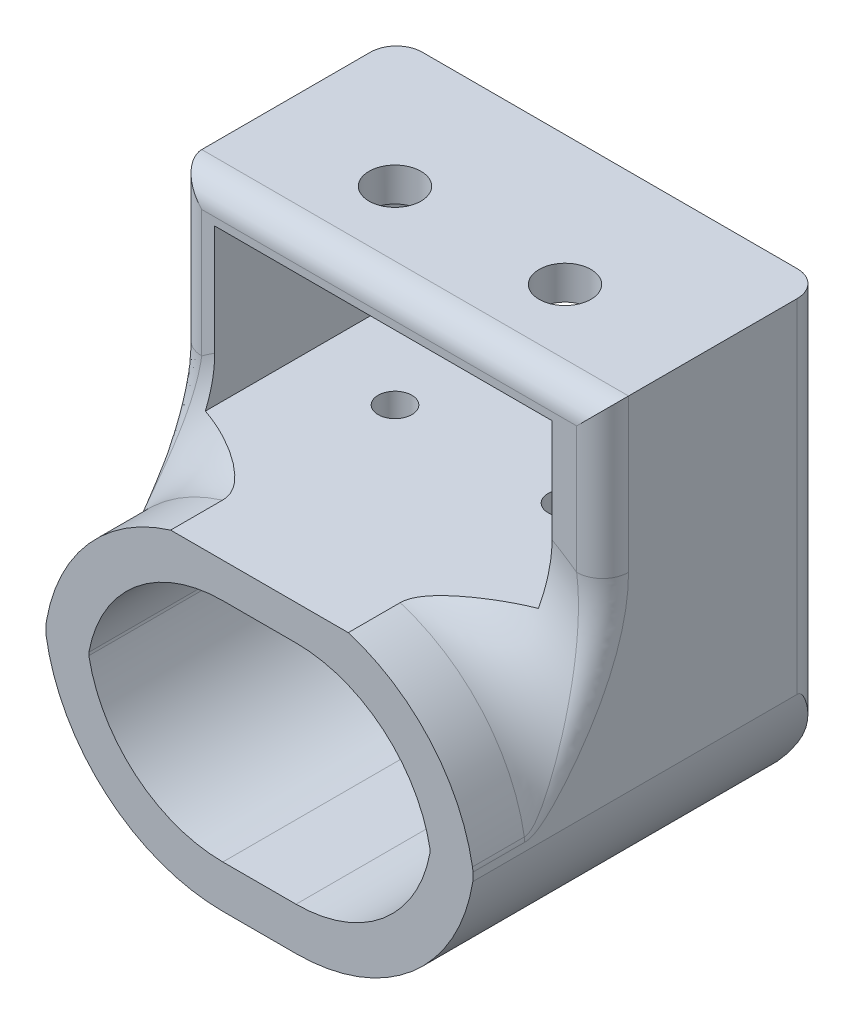
SolidWorks part; units mm, degrees
ref_plane "Front Plane" through (0, 0, 0) normal (0, 0, 1) x (1, 0, 0)
ref_plane "Top Plane" through (0, 0, 0) normal (0, 1, 0) x (1, 0, 0)
ref_plane "Right Plane" through (0, 0, 0) normal (1, 0, 0) x (0, 0, -1)
sketch "Sketch1" plane through (0, 0, 0) normal (0, 0, 1) x (1, 0, 0)
  line L2 (2.7649, 6.6874) -> (-0.0551, 6.6874)
  line L3 (-6.8689, 0.8749) -> (-6.8689, 0.48)
  line L4 (2.7649, 5.1874) -> (-0.0551, 5.1874)
  line L5 (-0.0551, -3.8326) -> (2.7649, -3.8326)
  line L6 (-0.0551, -5.3326) -> (2.7649, -5.3326)
  line L7 (-5.3689, 0.7486) -> (-5.3689, 0.6062)
  line L8 (8.0787, 0.7486) -> (8.0787, 0.6062)
  line L9 (9.5787, 0.8749) -> (9.5787, 0.48)
  arc A4 (8.0787, 0.7486) -> (2.7649, 5.1874) centre (2.7649, -0.2126) ccw
  arc A5 (-0.0551, 5.1874) -> (-5.3689, 0.7486) centre (-0.0551, -0.2126) ccw
  arc A6 (-5.3689, 0.6062) -> (-0.0551, -3.8326) centre (-0.0551, 1.5674) ccw
  arc A7 (2.7649, -3.8326) -> (8.0787, 0.6062) centre (2.7649, 1.5674) ccw
  arc A8 (-0.0551, 6.6874) -> (-6.8689, 0.8749) centre (-0.0551, -0.2126) ccw
  arc A9 (-6.8689, 0.48) -> (-0.0551, -5.3326) centre (-0.0551, 1.5674) ccw
  arc A10 (2.7649, -5.3326) -> (9.5787, 0.48) centre (2.7649, 1.5674) ccw
  arc A11 (9.5787, 0.8749) -> (2.7649, 6.6874) centre (2.7649, -0.2126) ccw
  dimension "D1" = 1.5
extrude "Boss-Extrude1" add sketch "Sketch1" along normal blind 12
sketch "Sketch2" plane through (0, 0, 0) normal (0, 0, -1) x (-1, 0, 0)
  line L4 (-9.5787, 0.8749) -> (-9.5787, 0.48)
  line L5 (-2.7649, -5.3326) -> (0.0551, -5.3326)
  line L6 (6.8689, 0.48) -> (6.8689, 0.8749)
  line L7 (0.0551, 6.6874) -> (-2.7649, 6.6874)
  line L8 (-9.5787, 0.8749) -> (-9.5787, 0.48)
  line L9 (-2.7649, -5.3326) -> (0.0551, -5.3326)
  line L10 (6.8689, 0.48) -> (6.8689, 0.8749)
  line L11 (0.0551, 6.6874) -> (-2.7649, 6.6874)
  arc A4 (-2.7649, 6.6874) -> (-9.5787, 0.8749) centre (-2.7649, -0.2126) ccw
  arc A5 (-9.5787, 0.48) -> (-2.7649, -5.3326) centre (-2.7649, 1.5674) ccw
  arc A6 (0.0551, -5.3326) -> (6.8689, 0.48) centre (0.0551, 1.5674) ccw
  arc A7 (6.8689, 0.8749) -> (0.0551, 6.6874) centre (0.0551, -0.2126) ccw
  arc A8 (-2.7649, 6.6874) -> (-9.5787, 0.8749) centre (-2.7649, -0.2126) ccw
  arc A9 (-9.5787, 0.48) -> (-2.7649, -5.3326) centre (-2.7649, 1.5674) ccw
  arc A10 (0.0551, -5.3326) -> (6.8689, 0.48) centre (0.0551, 1.5674) ccw
  arc A11 (6.8689, 0.8749) -> (0.0551, 6.6874) centre (0.0551, -0.2126) ccw
  dimension "D1" = 0
extrude "Boss-Extrude2" add sketch "Sketch2" along normal blind 1.5
sketch "Sketch3" plane through (0, 6.6874, 0) normal (0, 1, 0) x (1, 0, 0)
  line L0 (9.5787, -12) -> (9.5787, 1.5) construction
  line L1 (-6.8689, -12) -> (-6.8689, 1.5) construction
  line L2 (9.5787, -12) -> (9.5787, 1.5)
  line L3 (-6.8689, -12) -> (-6.8689, 1.5)
  line L4 (-6.8689, 1.5) -> (9.5787, 1.5)
  line L5 (-6.8689, -12) -> (9.5787, -12)
extrude "Boss-Extrude3" add sketch "Sketch3" along normal blind 7
sketch "Sketch4" plane through (0, 6.6874, 0) normal (0, -1, 0) x (1, 0, 0)
  line L4 (-0.0551, -1.5) -> (-0.0551, 12)
  line L5 (-0.0551, 12) -> (-6.8689, 12)
  line L6 (-6.8689, 12) -> (-6.8689, -1.5)
  line L7 (-6.8689, -1.5) -> (-0.0551, -1.5)
  line L8 (-0.0551, -1.5) -> (-0.0551, 12)
  line L9 (-0.0551, 12) -> (-6.8689, 12)
  line L10 (-6.8689, 12) -> (-6.8689, -1.5)
  line L11 (-6.8689, -1.5) -> (-0.0551, -1.5)
  dimension "D1" = 0
extrude "Boss-Extrude4" add sketch "Sketch4" along normal up to surface (5.8125 mm away) up to face at (-3.9976, 4.409, 5.25)
sketch "Sketch5" plane through (0, 6.6874, 0) normal (0, -1, 0) x (1, 0, 0)
  line L4 (9.5787, 12) -> (2.7649, 12)
  line L5 (2.7649, 12) -> (2.7649, -1.5)
  line L6 (2.7649, -1.5) -> (9.5787, -1.5)
  line L7 (9.5787, -1.5) -> (9.5787, 12)
  line L8 (9.5787, 12) -> (2.7649, 12)
  line L9 (2.7649, 12) -> (2.7649, -1.5)
  line L10 (2.7649, -1.5) -> (9.5787, -1.5)
  line L11 (9.5787, -1.5) -> (9.5787, 12)
  dimension "D1" = 0
extrude "Boss-Extrude5" add sketch "Sketch5" along normal up to surface up to face at (6.7074, 4.409, 5.25)
sketch "Sketch6" plane through (0, 0, 12) normal (0, 0, 1) x (1, 0, 0)
  line L0 (-5.3689, 12.3874) -> (7.6311, 12.3874)
  line L2 (7.6311, 12.3874) -> (7.6311, 6.3874)
  line L3 (-5.3689, 12.3874) -> (-5.3689, 6.3874)
  line L4 (-5.3689, 6.3874) -> (7.6311, 6.3874)
  dimension "D3" = 6
  dimension "D4" = 13
extrude "Cut-Extrude1" cut sketch "Sketch6" against normal blind 12
sketch "Sketch7" plane through (0, 13.6874, 0) normal (0, 1, 0) x (1, 0, 0)
  circle A0 centre (4.6311, -3.5) radius 1
  circle A1 centre (-1.9213, -3.5) radius 1
  dimension "D3" = 2
extrude "Cut-Extrude2" cut sketch "Sketch7" against normal blind 4
sketch "Sketch8" plane through (0, 6.3874, 0) normal (0, 1, 0) x (1, 0, 0)
  circle A4 centre (4.6311, -3.5) radius 0.65
  circle A5 centre (-1.9213, -3.5) radius 0.65
  dimension "D1" = 1.3
  dimension "D2" = 1.3
sketch "Sketch9" plane through (0, 0, 0) normal (0, 0, 1) x (1, 0, 0)
  line L6 (-5.2189, 0.7351) -> (-5.2189, 0.6198)
  line L7 (-5.2189, 0.7351) -> (-5.2189, 0.6198)
  line L16 (2.7649, 5.1874) -> (-0.0551, 5.1874) construction
  line L17 (-0.0551, -3.8326) -> (2.7649, -3.8326) construction
  line L18 (2.7649, 5.1874) -> (-0.0551, 5.1874)
  line L19 (2.7649, 5.0374) -> (-0.0551, 5.0374)
  line L20 (7.9287, 0.6198) -> (7.9287, 0.7351)
  line L21 (-0.0551, -3.6826) -> (2.7649, -3.6826)
  line L22 (2.7649, 5.0374) -> (-0.0551, 5.0374)
  line L23 (7.9287, 0.6198) -> (7.9287, 0.7351)
  line L24 (-0.0551, -3.6826) -> (2.7649, -3.6826)
  line L25 (-0.0551, -3.8326) -> (2.7649, -3.8326)
  line L26 (8.0787, 0.6062) -> (8.0787, 0.7486) construction
  line L27 (-5.3689, 0.7486) -> (-5.3689, 0.6062) construction
  line L28 (8.0787, 0.6062) -> (8.0787, 0.7486)
  line L29 (-5.3689, 0.7486) -> (-5.3689, 0.6062)
  arc A5 (-0.0551, 5.0374) -> (-5.2189, 0.7351) centre (-0.0551, -0.2126) ccw
  arc A6 (-5.2189, 0.6198) -> (-0.0551, -3.6826) centre (-0.0551, 1.5674) ccw
  arc A7 (-0.0551, 5.0374) -> (-5.2189, 0.7351) centre (-0.0551, -0.2126) ccw
  arc A8 (-5.2189, 0.6198) -> (-0.0551, -3.6826) centre (-0.0551, 1.5674) ccw
  arc A13 (2.7649, -3.8326) -> (8.0787, 0.6062) centre (2.7649, 1.5674) ccw construction
  arc A14 (8.0787, 0.7486) -> (2.7649, 5.1874) centre (2.7649, -0.2126) ccw construction
  arc A15 (7.9287, 0.7351) -> (2.7649, 5.0374) centre (2.7649, -0.2126) ccw
  arc A16 (2.7649, -3.6826) -> (7.9287, 0.6198) centre (2.7649, 1.5674) ccw
  arc A17 (7.9287, 0.7351) -> (2.7649, 5.0374) centre (2.7649, -0.2126) ccw
  arc A18 (2.7649, -3.6826) -> (7.9287, 0.6198) centre (2.7649, 1.5674) ccw
  arc A19 (-0.0551, 5.1874) -> (-5.3689, 0.7486) centre (-0.0551, -0.2126) ccw construction
  arc A20 (-5.3689, 0.6062) -> (-0.0551, -3.8326) centre (-0.0551, 1.5674) ccw construction
  arc A21 (2.7649, -3.8326) -> (8.0787, 0.6062) centre (2.7649, 1.5674) ccw
  arc A22 (8.0787, 0.7486) -> (2.7649, 5.1874) centre (2.7649, -0.2126) ccw
  arc A23 (-0.0551, 5.1874) -> (-5.3689, 0.7486) centre (-0.0551, -0.2126) ccw
  arc A24 (-5.3689, 0.6062) -> (-0.0551, -3.8326) centre (-0.0551, 1.5674) ccw
  dimension "D1" = 0.15
  dimension "D2" = 0.15
extrude "Boss-Extrude6" add sketch "Sketch9" along normal up to surface (12 mm away) up to face at (1.1311, 9.3874, 12)
sketch "Sketch11" plane through (0, 0, 12) normal (0, 0, 1) x (1, 0, 0)
  line L5 (-6.8689, 13.6874) -> (9.5787, 13.6874) construction
  line L6 (7.6311, 6.3874) -> (7.6311, 12.3874) construction
  line L7 (7.6311, 12.3874) -> (-5.3689, 12.3874) construction
  line L8 (-5.3689, 12.3874) -> (-5.3689, 6.3874) construction
  line L9 (-5.3689, 6.3874) -> (7.6311, 6.3874) construction
  line L10 (9.5787, 0.48) -> (9.5787, 13.6874) construction
  line L11 (-6.8689, 13.6874) -> (-6.8689, 0.48) construction
  line L12 (-6.8689, 13.6874) -> (9.5787, 13.6874)
  line L13 (7.6311, 6.3874) -> (7.6311, 12.3874)
  line L14 (7.6311, 12.3874) -> (-5.3689, 12.3874)
  line L15 (-5.3689, 12.3874) -> (-5.3689, 6.3874)
  line L16 (-5.3689, 6.3874) -> (7.6311, 6.3874)
  line L17 (9.5787, 0.8749) -> (9.5787, 13.6874)
  line L18 (-6.8689, 13.6874) -> (-6.8689, 0.8749)
  arc A4 (4.7774, 6.3874) -> (9.5787, 0.8749) centre (2.7649, -0.2126) cw
  arc A5 (-6.8689, 0.8749) -> (-2.0676, 6.3874) centre (-0.0551, -0.2126) cw
  line M12 (7.6311, 12.3874) -> (7.6311, 6.3874)
  line M13 (7.6311, 6.3874) -> (-5.3689, 6.3874)
  line M14 (-5.3689, 6.3874) -> (-5.3689, 12.3874)
  line M15 (-5.3689, 12.3874) -> (7.6311, 12.3874)
  line M16 (9.5787, 13.6874) -> (-6.8689, 13.6874)
  line M17 (-6.8689, 13.6874) -> (-6.8689, 0.48)
  line M21 (9.5787, 0.48) -> (9.5787, 13.6874)
extrude "Cut-Extrude4" cut sketch "Sketch11" against normal blind 5 contours A5 A4 M17 M13 M14 M15 M12 M21 M16 region at (1.3549, 13.479, 12)
sketch "Sketch12" plane through (0, 0, 0) normal (0, 0, 1) x (1, 0, 0)
  line L4 (7.6311, 6.3874) -> (7.6311, 12.3874)
  line L5 (7.6311, 12.3874) -> (-5.3689, 12.3874)
  line L6 (-5.3689, 12.3874) -> (-5.3689, 6.3874)
  line L7 (-5.3689, 6.3874) -> (7.6311, 6.3874)
  line L8 (7.6311, 6.3874) -> (7.6311, 12.3874)
  line L9 (7.6311, 12.3874) -> (-5.3689, 12.3874)
  line L10 (-5.3689, 12.3874) -> (-5.3689, 6.3874)
  line L11 (-5.3689, 6.3874) -> (7.6311, 6.3874)
  dimension "D1" = 0
extrude "Cut-Extrude5" cut sketch "Sketch12" against normal blind 5
extrude "Cut-Extrude6" cut sketch "Sketch8" against normal blind 5
fillet "Fillet1" radius 3 2 edges at (7.968, 4.3193, 7) (-5.2582, 4.3193, 7)
fillet "Fillet2" radius 1 7 edges at (9.5787, 0.8749, 11) (9.5787, 1.2273, 9.3826) (-6.8689, 0.8749, 11) (-6.8689, 10.3285, 7) (9.5787, 10.3285, 7) (1.3549, 13.6874, 7) (-6.8689, 1.0577, 9.5687)
fillet "Fillet3" radius 1 2 edges at (-6.8689, 7.0837, -1.5) (9.5787, 7.0837, -1.5)
